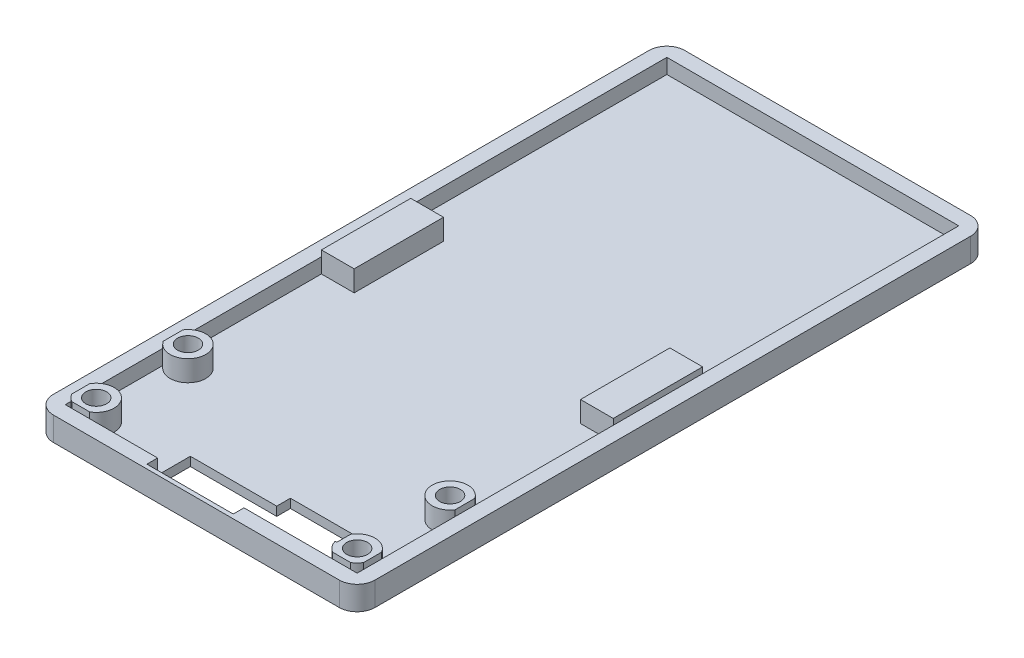
SolidWorks part; units mm, degrees
ref_plane "Front Plane" through (0, 0, 0) normal (0, 0, 1) x (1, 0, 0)
ref_plane "Top Plane" through (0, 0, 0) normal (0, 1, 0) x (1, 0, 0)
ref_plane "Right Plane" through (0, 0, 0) normal (1, 0, 0) x (0, 0, -1)
sketch "Sketch1" plane through (0, 0, 0) normal (0, 1, 0) x (1, 0, 0)
  line L1 (-24.5, -50.5) -> (24.5, -50.5)
  line L2 (-24.5, -50.5) -> (-24.5, 50.5)
  line L3 (-24.5, 50.5) -> (24.5, 50.5)
  line L4 (24.5, -50.5) -> (24.5, 50.5)
  line L5 (-24.5, -50.5) -> (24.5, 50.5) construction
  line L6 (-24.5, 50.5) -> (24.5, -50.5) construction
  point P0 (0, 0)
  dimension "D1" = 49
  dimension "D2" = 101
extrude "Boss-Extrude1" add sketch "Sketch1" along normal blind 1.5
sketch "Sketch2" plane through (0, 0, 0) normal (0, 1, 0) x (1, 0, 0)
  line L4 (24.5, -50.5) -> (24.5, 50.5)
  line L5 (24.5, 50.5) -> (-24.5, 50.5)
  line L6 (-24.5, 50.5) -> (-24.5, -50.5)
  line L7 (-24.5, -50.5) -> (24.5, -50.5)
  line L8 (24.5, -50.5) -> (24.5, 50.5)
  line L9 (24.5, 50.5) -> (-24.5, 50.5)
  line L10 (-24.5, 50.5) -> (-24.5, -50.5)
  line L11 (-24.5, -50.5) -> (24.5, -50.5)
  line L16 (27, -53) -> (27, 53)
  line L17 (27, 53) -> (-27, 53)
  line L18 (-27, 53) -> (-27, -53)
  line L19 (-27, -53) -> (27, -53)
  line L20 (27, -53) -> (27, 53)
  line L21 (27, 53) -> (-27, 53)
  line L22 (-27, 53) -> (-27, -53)
  line L23 (-27, -53) -> (27, -53)
  dimension "D1" = 0
  dimension "D2" = 2.5
extrude "Boss-Extrude2" add sketch "Sketch2" along normal blind 4
sketch "Sketch3" plane through (0, 0, 0) normal (0, 1, 0) x (1, 0, 0)
  line L0 (24.5, -50.5) -> (-24.5, -50.5) construction
  line L1 (-24.5, -50.5) -> (-24.5, 50.5) construction
  line L2 (-24.5, 50.5) -> (-24.5, -50.5) construction
  line L3 (-24.5, -30.7417) -> (-24.5, -34.0583)
  line L4 (-24.5, -7.5) -> (-19, -7.5)
  line L5 (-24.5, -7.5) -> (-24.5, 7.5)
  line L6 (-24.5, 7.5) -> (-19, 7.5)
  line L7 (-19, -7.5) -> (-19, 7.5)
  line L8 (-24.5, -46.4033) -> (-24.5, -49.3967)
  line L9 (-24.5, 50.5) -> (-24.5, -50.5) construction
  line L10 (-23.3967, -50.5) -> (-20.4033, -50.5)
  line L11 (-24.5, -50.5) -> (24.5, -50.5) construction
  arc A0 (-24.5, -49.3967) -> (-23.3967, -50.5) centre (-21.9, -47.9) ccw
  arc A1 (-24.5, -34.0583) -> (-24.5, -30.7417) centre (-22, -32.4) ccw
  arc A2 (-20.4033, -50.5) -> (-24.5, -46.4033) centre (-21.9, -47.9) ccw
  point P15 (-19, 0)
  dimension "D2" = 2.6
  dimension "D5" = 6
  dimension "D7" = 6
  dimension "D1" = 2.6
  dimension "D3" = 2.5
  dimension "D4" = 18.1
  dimension "D6" = 15
extrude "Boss-Extrude3" add sketch "Sketch3" along normal offset from surface (5 mm away) 1 up to face at (0, 4, 0) offset beyond the face yes
mirror "Mirror1" about plane through (0, 0, 0) normal (1, 0, 0) of "Boss-Extrude3"
sketch "Sketch4" plane through (0, 5, 0) normal (0, 1, 0) x (1, 0, 0)
  circle A0 centre (-21.9, -47.9) radius 1.75
  circle A1 centre (21.9, -47.9) radius 1.75
  dimension "D1" = 3.5
  dimension "D2" = 3.5
extrude "Cut-Extrude1" cut sketch "Sketch4" against normal blind 4.25
sketch "Sketch5" plane through (0, 5, 0) normal (0, 1, 0) x (1, 0, 0)
  circle A0 centre (-22, -32.4) radius 1.75
  circle A1 centre (22, -32.4) radius 1.75
  dimension "D1" = 3.5
  dimension "D2" = 3.5
extrude "Cut-Extrude2" cut sketch "Sketch5" against normal blind 4.25
sketch "Sketch6" plane through (0, 0, 0) normal (0, 1, 0) x (1, 0, 0)
  line L1 (-9, -45) -> (5.5, -45)
  line L2 (-9, -45) -> (-9, -52.3)
  line L3 (-9, -52.3) -> (5.5, -52.3)
  line L4 (5.5, -45) -> (5.5, -52.3)
  line L8 (-23.3967, -50.5) -> (20.4033, -50.5) construction
  line L10 (24.5, -46.4033) -> (24.5, -34.0583) construction
  line L11 (-24.5, -34.0583) -> (-24.5, -46.4033) construction
  line L13 (-27, -53) -> (27, -53) construction
  dimension "D1" = 15.5
  dimension "D2" = 19
  dimension "D3" = 0.7
  dimension "D4" = 5.5
extrude "Cut-Extrude3" cut sketch "Sketch6" along normal through all
sketch "Sketch7" plane through (0, 0, 0) normal (0, 1, 0) x (1, 0, 0)
  line L0 (-27, -53) -> (27, -53) construction
  line L1 (19.3, -48.7) -> (5.5, -48.7)
  line L2 (19.3, -48.7) -> (19.3, -42.7)
  line L3 (19.3, -42.7) -> (5.5, -42.7)
  line L4 (5.5, -48.7) -> (5.5, -42.7)
  line L5 (5.5, -52.3) -> (5.5, -45) construction
  line L7 (27, -53) -> (27, 53) construction
  point P4 (19.3, -45.7)
  point P10 (12.4, -42.7)
  dimension "D1" = 13.8
  dimension "D2" = 7.3
  dimension "D3" = 6
  dimension "D5" = 14.6
extrude "Cut-Extrude4" cut sketch "Sketch7" along normal through all
fillet "Fillet1" radius 3 4 edges at (-27, 2, 53) (27, 2, 53) (27, 2, -53) (-27, 2, -53)
